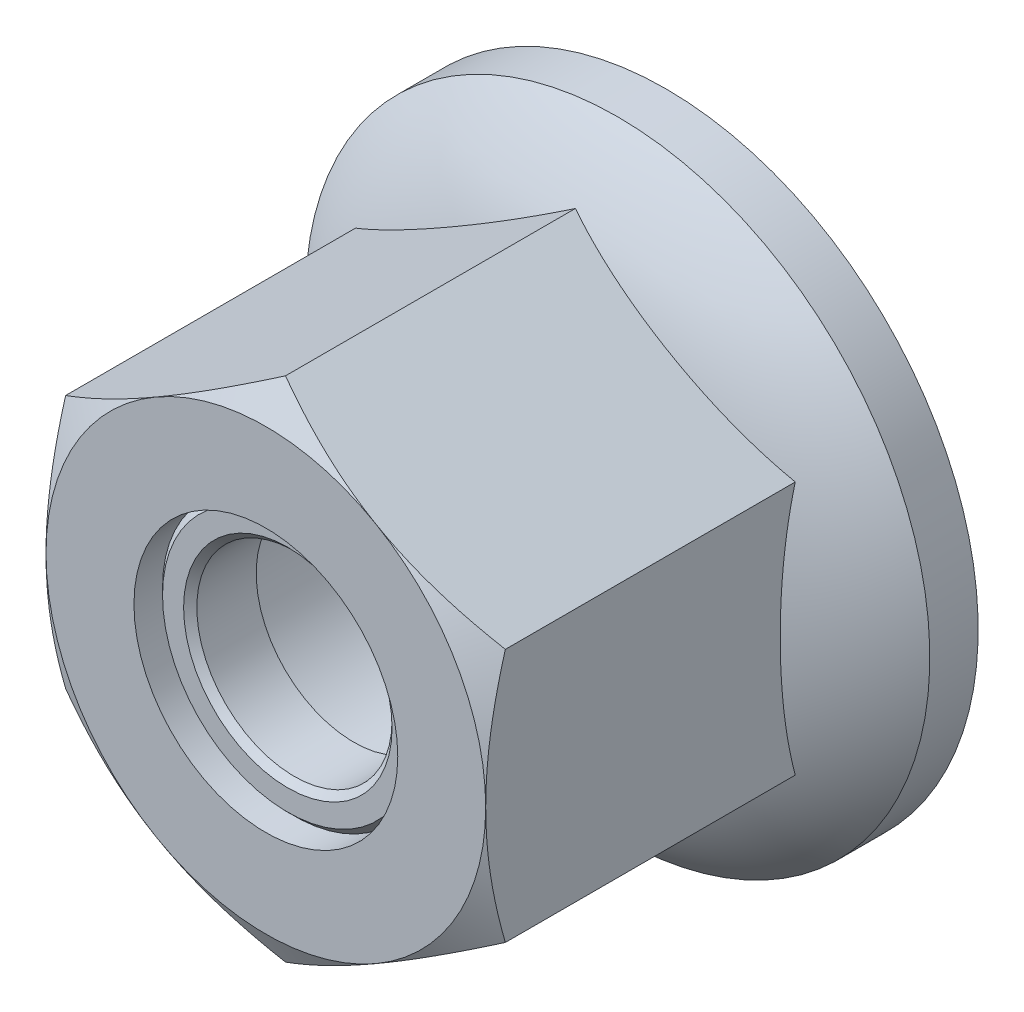
SolidWorks part; units mm, degrees
material "Alloy Steel"
ref_plane "Front Plane" through (0, 0, 0) normal (0, 0, 1) x (1, 0, 0)
ref_plane "Top Plane" through (0, 0, 0) normal (0, 1, 0) x (1, 0, 0)
ref_plane "Right Plane" through (0, 0, 0) normal (1, 0, 0) x (0, 0, -1)
sketch "Sketch1" plane through (0, 0, 0) normal (0, 0, 1) x (1, 0, 0)
  line L1 (0, 5.7735) -> (-5, 2.8868)
  line L2 (-5, 2.8868) -> (-5, -2.8868)
  line L3 (-5, -2.8868) -> (0, -5.7735)
  line L4 (0, -5.7735) -> (5, -2.8868)
  line L5 (5, -2.8868) -> (5, 2.8868)
  line L6 (5, 2.8868) -> (0, 5.7735)
  circle A0 centre (0, 0) radius 5 construction
  circle A1 centre (0, 0) radius 3
  dimension "Thread Size" = 6
  dimension "Hex" = 10
extrude "Extrude1" add sketch "Sketch1" against normal blind 9.1
sketch "Sketch2" plane through (0, 0, 0) normal (0, 0, 1) x (1, 0, 0)
  circle A0 centre (0, 0) radius 5 construction
  circle A1 centre (0, 0) radius 5
extrude "Cut-Extrude1" cut sketch "Sketch2" against normal through all draft 60 flip side to cut
sketch "Sketch3" plane through (0, 0, 0) normal (1, 0, 0) x (0, 0, -1)
  line L0 (9.1, 7.1) -> (9.1, 3)
  line L1 (9.1, 3) -> (6.35, 3)
  line L2 (9.1, 7.1) -> (8, 7.1)
  line L3 (0, 0) -> (9.1, 0) construction
  line L4 (0, -2.8868) -> (0, 2.8868) construction
  line L5 (9.1, -2.8868) -> (9.1, 2.8868) construction
  line L6 (9.1, 2.8868) -> (9.1, 5.7735) construction
  line L7 (9.1, -3) -> (9.1, 3) construction
  line L8 (6.35, 3) -> (6.35, 7.1) construction
  arc A0 (8, 7.1) -> (6.35, 3) centre (12.2689, 3) ccw
  dimension "Flange OD" = 14.2
  dimension "Flange Thickness" = 1.1
  dimension "D1" = 1.65
revolve "Revolve1" add sketch "Sketch3" angle 360 about L3
sketch "Sketch5" plane through (0, 0, 0) normal (0, 0, 1) x (1, 0, 0)
  circle A1 centre (0, 0) radius 3
  circle A2 centre (0, 0) radius 3 construction
curve "Helix/Spiral1" [suppressed] pitch 1 height 10.1 turns 10.1 parameters "pitch"=1
sketch "Sketch10" plane through (0, 0, 0) normal (0, 0, 1) x (1, 0, 0)
  circle A1 centre (0, 0) radius 3 construction
  circle A2 centre (0, 0) radius 2.2206
  circle A3 centre (0, 0) radius 2.2206
  circle A4 centre (0, 0) radius 3
  dimension "D1" = 0.7794
extrude "Boss-Extrude1" add sketch "Sketch10" against normal blind 1.5 from offset 0.5 separate body offset against normal yes
chamfer "Chamfer1" distance 0.15 angle 45 2 edges at (3, 0, -0.5) (2.2206, 0, -0.5)
sketch "Sketch6" [suppressed] plane through (0, 0, 0) normal (1, 0, 0) x (0, 0, -1)
  line L0 (-0.875, 3) -> (0, 3)
  line L1 (-0.875, 3) -> (-0.5, 2.3505)
  line L2 (-0.5, 2.3505) -> (-0.375, 2.3505)
  line L3 (-0.375, 2.3505) -> (0, 3)
  line L4 (-0.4375, 2.3505) -> (-0.4375, 3) construction
  line L5 (-0.6875, 2.6752) -> (-0.1875, 2.6752) construction
  dimension "D1" = 60
  dimension "D2" = 0.125
  dimension "D3" = 0.5
  dimension "D4" = 0.6495
sweep "Sweep1" [suppressed] add profiles "Sketch6" path "Helix/Spiral1"
sketch "Sketch7" [suppressed] plane through (0, 0, -2) normal (0, 0, 1) x (1, 0, 0)
  circle A1 centre (0, 0) radius 3
  circle A2 centre (0, 0) radius 3
  dimension "D1" = 0
extrude "Cut-Extrude2" [suppressed] cut sketch "Sketch7" against normal through all draft 45 and the other way through all
sketch "Sketch8" [suppressed] plane through (0, 0, -9.1) normal (0, 0, -1) x (-1, 0, 0)
  circle A0 centre (0, 0) radius 3.1
  circle A1 centre (0, 0) radius 3
  circle A2 centre (0, 0) radius 3 construction
  dimension "D1" = 0
  dimension "D2" = 0.1
extrude "Cut-Extrude3" [suppressed] cut sketch "Sketch8" against normal through all draft 45 and the other way through all draft 45
ref_axis "Center Axis 1" [suppressed] through (0, 0, -11.2049) along (0, 0, 1)
ref_plane "Contact Plane 1" [suppressed] through (0, 0, -9.1) normal (0, 0, -1) x (-1, 0, 0)
equation "\"D3@Helix/Spiral1\" = \"pitch@Helix/Spiral1\"+\"Height@Extrude1\""
equation "\"D2@Sketch6\"=\"pitch@Helix/Spiral1\"*.125"
equation "\"D3@Sketch6\"=\"pitch@Helix/Spiral1\"*.50"
equation "\"D1@Sketch10\"=\"D4@Sketch6\"*1.2"
equation "\"D1@Boss-Extrude1\"=\"pitch@Helix/Spiral1\"*1.5"
equation "\"D1@Sketch3\"=\"Flange Thickness@Sketch3\"*1.5"
